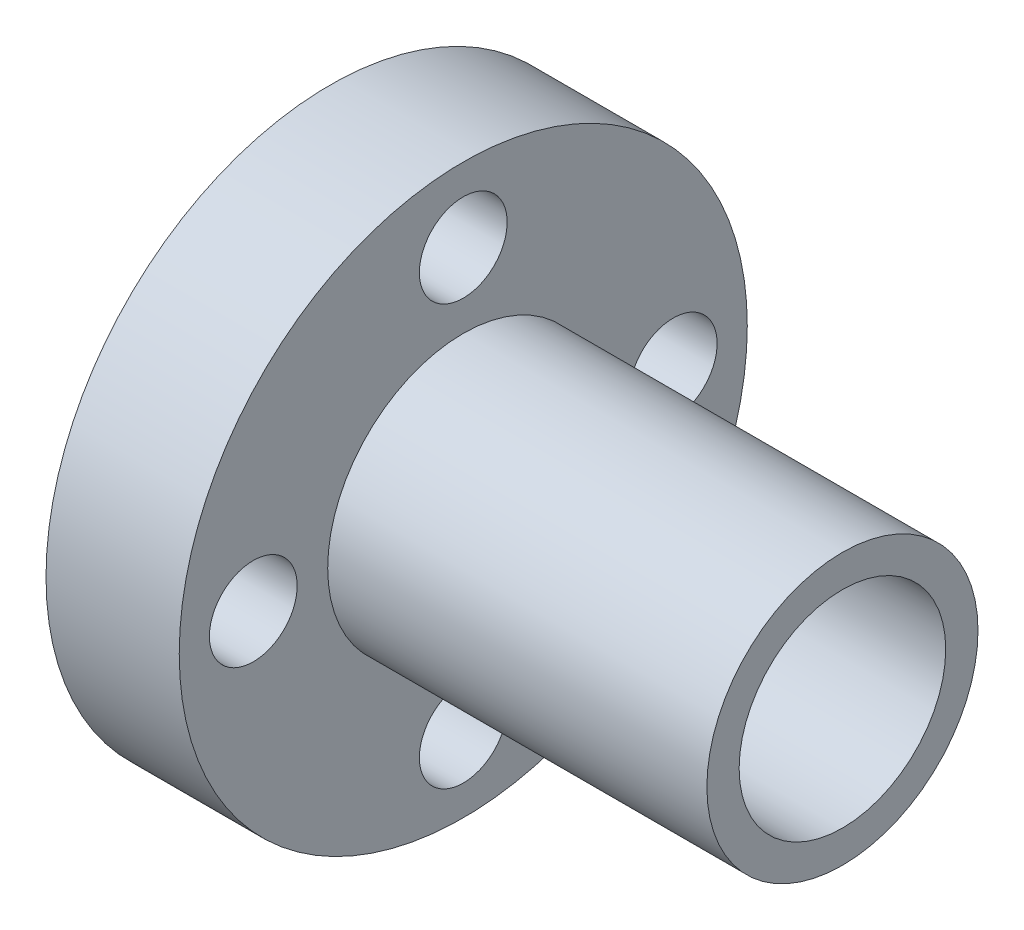
SolidWorks part; units mm, degrees
material "Brass"
ref_plane "Front" through (0, 0, 0) normal (0, 0, 1) x (1, 0, 0)
ref_plane "Top" through (0, 0, 0) normal (0, 1, 0) x (1, 0, 0)
ref_plane "Right" through (0, 0, 0) normal (1, 0, 0) x (0, 0, -1)
sketch "Sketch1" plane through (0, 0, 0) normal (1, 0, 0) x (0, 0, -1)
  line L0 (0, 0) -> (-2.5, 0) construction
  circle A0 centre (0, 0) radius 4 construction
  circle A2 centre (0, 0) radius 2.75
  dimension "Diameter" = 8
  dimension "D1" = 5.5
  dimension "Pitch" = 2.5
extrude "Boss-Extrude1" [suppressed] add sketch "Sketch1" along normal blind 38.1 and the other way blind 2.54
sketch "Sketch3" [suppressed] plane through (-2.54, 0, 0) normal (-1, 0, 0) x (0, 0, 1)
  circle A1 centre (0, 0) radius 2.75
  circle A2 centre (0, 0) radius 2.75
  dimension "D1" = 0
curve "Helix/Spiral1" [suppressed] pitch 10 height 40.64 turns 4.064 parameters "Travel-per-turn"=10
sketch "Sketch2" [suppressed] plane through (0, 0, 0) normal (0, 0, 1) x (1, 0, 0)
  line L0 (-0.1091, 1.0461) -> (-0.1091, 3.375) construction
  line L1 (0, 0) -> (-2.5, 0) construction
  line L2 (-0.1091, 1.0461) -> (-1.3591, 5.7112) construction
  line L3 (1.1409, 5.7112) -> (-1.3591, 5.7112) construction
  line L4 (-0.1091, 1.0461) -> (1.1409, 5.7112) construction
  line L5 (-0.1091, 3.375) -> (-0.1091, 5.7112) construction
  line L6 (-0.1091, 3.375) -> (1.4446, 3.375) construction
  line L7 (-0.3664, 2.75) -> (-0.1091, 2.75) construction
  line L8 (-2.54, 2.75) -> (-0.1091, 2.75)
  line L9 (-0.1091, 4) -> (-0.3664, 4) construction
  line L10 (-0.3664, 4) -> (-0.3664, 2.75) construction
  line L11 (-0.3664, 3.375) -> (-0.1091, 3.375) construction
  line L12 (38.1, 2.75) -> (-2.54, 2.75) construction
  line L13 (-1.3246, 3.4475) -> (-1.3246, 4) construction
  line L14 (-0.7909, 3.5905) -> (-0.6838, 3.191)
  line L15 (-1.8582, 3.5905) -> (-1.9653, 3.191)
  circle A0 centre (-1.3246, 3.4475) radius 0.5525 construction
  circle A1 centre (-0.1091, 3.345) radius 0.595 construction
  arc A2 (-1.3246, 4) -> (-0.7909, 3.5905) centre (-1.3246, 3.4475) cw
  arc A3 (-0.1091, 2.75) -> (-0.6838, 3.191) centre (-0.1091, 3.345) cw
  arc A4 (-1.3246, 4) -> (-1.8582, 3.5905) centre (-1.3246, 3.4475) ccw
  arc A5 (-1.9653, 3.191) -> (-2.54, 2.75) centre (-2.54, 3.345) cw
  dimension "Pitch" = 2.5
  dimension "D3" = 1.19
  dimension "D4" = 1.105
  dimension "D1" = 30
  dimension "D2" = 1.25
sweep "Sweep1" [suppressed] add profiles "Sketch2" path "Helix/Spiral1"
ref_axis "Axis2" [suppressed] through (38.1058, 0, 0) along (-1, 0, 0)
pattern_circular "CirPattern1" [suppressed] count 4 over 360 about axis through (38.1058, 0, 0) along (-1, 0, 0) of bodies 140
sketch "Sketch4" plane through (0, 0, 0) normal (1, 0, 0) x (0, 0, -1)
  circle A0 centre (0, 0) radius 11
  dimension "A" = 22
extrude "Boss-Extrude2" add sketch "Sketch4" along normal blind 5.1594 separate body
sketch "Sketch5" plane through (0, 0, 0) normal (-1, 0, 0) x (0, 0, 1)
  circle A0 centre (0, 0) radius 5.25
  dimension "D1" = 10.5
extrude "Boss-Extrude3" add sketch "Sketch5" against normal blind 19.8438
sketch "Sketch6" plane through (0, 0, 0) normal (1, 0, 0) x (0, 0, -1)
  line L0 (0, 0) -> (0, 8.1315) construction
  circle A0 centre (0, 0) radius 8.1315 construction
  circle A1 centre (0, 8.1315) radius 1.7
  dimension "D1" = 16.263
  dimension "D2" = 3.4
extrude "Cut-Extrude1" cut sketch "Sketch6" along normal up to surface (5.1594 mm away) up to face at (5.1594, 0, -5.25)
ref_axis "Axis3" through (5.1594, 0, 0) along (-1, 0, 0)
pattern_circular "CirPattern2" count 4 over 360 about axis through (5.1594, 0, 0) along (-1, 0, 0) of "Cut-Extrude1"
combine bodies "Combine1" [suppressed] operation type add bodies to combine 148 141
sketch "Sketch7" plane through (0, 0, 0) normal (1, 0, 0) x (0, 0, -1)
  circle A0 centre (0, 0) radius 4 construction
  circle A1 centre (0, 0) radius 4 construction
  circle A2 centre (0, 0) radius 4.2
  dimension "D1" = 8
  dimension "D2" = 8.4
extrude "Cut-Extrude2" [suppressed] cut sketch "Sketch7" along normal blind 6.35 draft 60
ref_plane "Plane5" through (9.9219, 0, 0) normal (-1, 0, 0) x (0, 0, 1)
mirror "Mirror1" [suppressed] about plane through (9.9219, 0, 0) normal (-1, 0, 0)
sketch "Sketch8" plane through (19.8438, 0, 0) normal (1, 0, 0) x (0, 0, -1)
  circle A0 centre (0, 0) radius 4.0005
  dimension "D1" = 8.001
extrude "Cut-Extrude3" cut sketch "Sketch8" against normal through all
equation "\"D1@Sketch1\" = \"Diameter@Sketch1\"-\"Pitch@Sketch1\""
equation "\"D2@Sketch2\" = \"Pitch@Sketch2\"/2"
equation "\"D3@Sketch2\" = 2*.238*\"Pitch@Sketch2\""
equation "\"D4@Sketch2\" = \"Pitch@Sketch2\"*2*.221"
equation "\"D2@Sketch7\" = \"D1@Sketch7\"*1.05"
